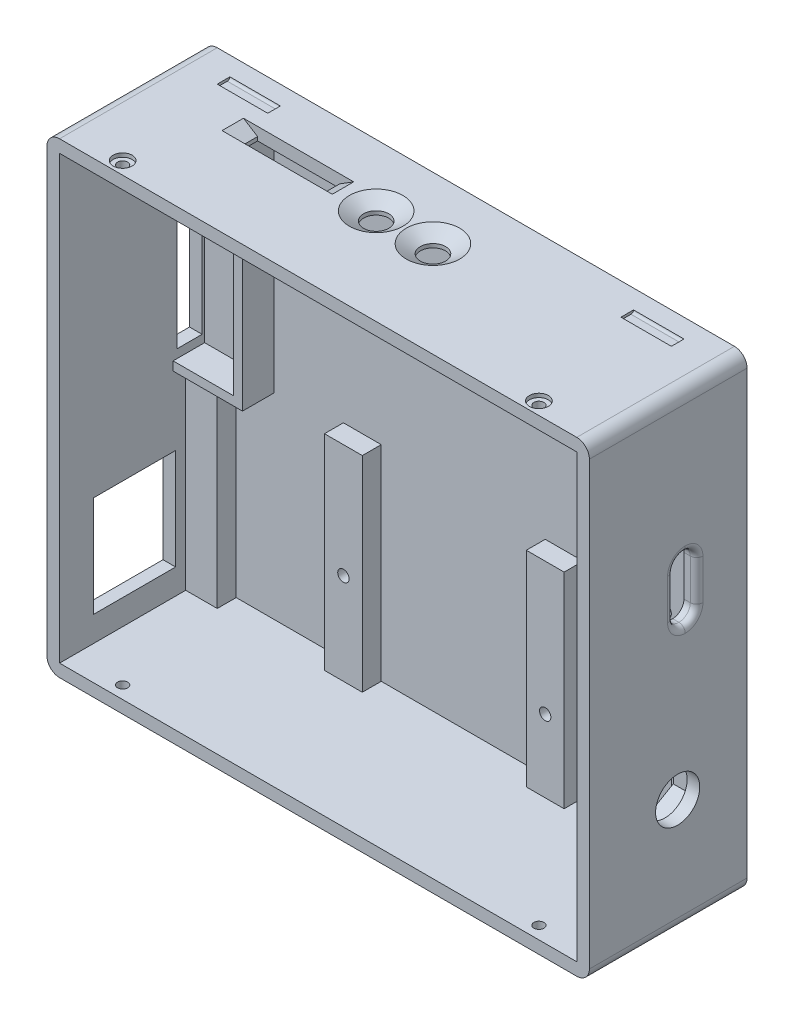
SolidWorks part; units mm, degrees
ref_plane "Front Plane" through (0, 0, 0) normal (0, 0, 1) x (1, 0, 0)
ref_plane "Top Plane" through (0, 0, 0) normal (0, 1, 0) x (1, 0, 0)
ref_plane "Right Plane" through (0, 0, 0) normal (1, 0, 0) x (0, 0, -1)
sketch "Sketch1" plane through (0, 0, 0) normal (0, 0, 1) x (1, 0, 0)
  line L1 (0, 0) -> (86, 0)
  line L2 (0, 0) -> (0, 74)
  line L3 (0, 74) -> (86, 74)
  line L4 (86, 0) -> (86, 74)
  dimension "D1" = 74
  dimension "D2" = 86
extrude "Boss-Extrude1" add sketch "Sketch1" along normal blind 25
sketch "Sketch3" plane through (0, 0, 25) normal (0, 0, 1) x (1, 0, 0)
  line L0 (0, 74) -> (0, 0) construction
  line L1 (2, 72) -> (84, 72)
  line L2 (2, 72) -> (2, 2)
  line L3 (2, 2) -> (84, 2)
  line L4 (84, 72) -> (84, 2)
  line L5 (86, 74) -> (0, 74) construction
  line L6 (0, 0) -> (86, 0) construction
  line L7 (86, 0) -> (86, 74) construction
  dimension "D1" = 2
  dimension "D2" = 2
  dimension "D3" = 2
  dimension "D4" = 2
extrude "Cut-Extrude1" cut sketch "Sketch3" against normal blind 23
sketch "Sketch4" plane through (0, 0, 2) normal (0, 0, 1) x (1, 0, 0)
  line L0 (84, 72) -> (2, 72) construction
  line L1 (84, 72) -> (76, 72)
  line L2 (84, 72) -> (84, 34.5)
  line L3 (84, 34.5) -> (76, 34.5)
  line L4 (76, 72) -> (76, 34.5)
  line L5 (13, 72) -> (11.6, 72)
  line L6 (13, 72) -> (13, 34.5)
  line L7 (13, 34.5) -> (11.6, 34.5)
  line L8 (11.6, 72) -> (11.6, 34.5)
  line L9 (84, 2) -> (84, 72) construction
  dimension "D1" = 37.5
  dimension "D2" = 8
  dimension "D3" = 71
  dimension "D4" = 1.4
extrude "Boss-Extrude2" add sketch "Sketch4" along normal blind 5
sketch "Sketch5" plane through (0, 0, 7) normal (0, 0, 1) x (1, 0, 0)
  line L0 (76, 72) -> (76, 34.5) construction
  line L1 (76, 54) -> (79, 54)
  line L2 (76, 54) -> (76, 62)
  line L3 (76, 62) -> (79, 62)
  line L4 (79, 54) -> (79, 62)
  line L5 (84, 72) -> (76, 72) construction
  line L6 (84, 34.5) -> (84, 72) construction
  line L7 (76, 34.5) -> (84, 34.5) construction
  line L8 (76, 41.5) -> (77, 41.5)
  line L9 (76, 41.5) -> (76, 45.5)
  line L10 (76, 45.5) -> (77, 45.5)
  line L11 (77, 41.5) -> (77, 45.5)
  dimension "D1" = 8
  dimension "D2" = 18
  dimension "D3" = 5
  dimension "D4" = 7
  dimension "D5" = 7
  dimension "D6" = 4
extrude "Cut-Extrude2" cut sketch "Sketch5" against normal blind 2
sketch "Sketch6" plane through (0, 0, 7) normal (0, 0, 1) x (1, 0, 0)
  line L0 (84, 72) -> (76, 72) construction
  line L2 (84, 34.5) -> (84, 72) construction
  circle A0 centre (80, 67.25) radius 1
  circle A1 centre (80, 39.25) radius 1
  dimension "D4" = 2
  dimension "D5" = 2
  dimension "D1" = 28
  dimension "D2" = 4.75
  dimension "D3" = 4
extrude "Cut-Extrude3" cut sketch "Sketch6" against normal blind 5
sketch "Sketch7" plane through (2, 0, 0) normal (1, 0, 0) x (0, 0, -1)
  line L1 (-2.4, 70.85) -> (-6.4, 70.85)
  line L2 (-2.4, 70.85) -> (-2.4, 35.85)
  line L3 (-2.4, 35.85) -> (-6.4, 35.85)
  line L4 (-6.4, 70.85) -> (-6.4, 35.85)
  line L5 (-2, 72) -> (-2, 2) construction
  line L6 (-2, 72) -> (-25, 72) construction
  dimension "D1" = 4
  dimension "D2" = 35
  dimension "D3" = 0.4
  dimension "D4" = 1.15
extrude "Cut-Extrude4" cut sketch "Sketch7" against normal blind 5
sketch "Sketch9" plane through (0, 0, 2) normal (0, 0, 1) x (1, 0, 0)
  line L0 (2, 2) -> (84, 2) construction
  line L1 (84, 34.5) -> (79, 34.5)
  line L2 (84, 34.5) -> (84, 2)
  line L3 (84, 2) -> (79, 2)
  line L4 (79, 34.5) -> (79, 2)
  line L6 (62, 2) -> (56, 2)
  line L7 (62, 2) -> (62, 34.5)
  line L8 (62, 34.5) -> (56, 34.5)
  line L9 (56, 2) -> (56, 34.5)
  line L10 (2, 2) -> (7, 2)
  line L11 (2, 2) -> (2, 34.5)
  line L12 (2, 34.5) -> (7, 34.5)
  line L13 (7, 2) -> (7, 34.5)
  line L14 (24, 2) -> (30, 2)
  line L15 (24, 2) -> (24, 34.5)
  line L16 (24, 34.5) -> (30, 34.5)
  line L17 (30, 2) -> (30, 34.5)
  dimension "D1" = 5
  dimension "D2" = 6
  dimension "D3" = 22
  dimension "D4" = 5
  dimension "D5" = 6
  dimension "D6" = 22
extrude "Boss-Extrude3" add sketch "Sketch9" along normal blind 3
sketch "Sketch10" plane through (0, 0, 5) normal (0, 0, 1) x (1, 0, 0)
  line L0 (84, 2) -> (84, 34.5) construction
  line L1 (56, 2) -> (62, 2) construction
  line L2 (27, 34.5) -> (27, 2) construction
  line L3 (30, 34.5) -> (24, 34.5) construction
  line L4 (24, 2) -> (30, 2) construction
  circle A0 centre (59, 13.5) radius 0.9
  circle A1 centre (27, 16.5) radius 0.9
  dimension "D3" = 1.8
  dimension "D4" = 1.8
  dimension "D1" = 25
  dimension "D2" = 11.5
  dimension "D5" = 14.5
extrude "Cut-Extrude6" cut sketch "Sketch10" against normal blind 4
fillet "Fillet1" radius 2 4 edges at (86, 74, 12.5) (0, 74, 12.5) (0, 0, 12.5) (86, 0, 12.5)
sketch "Sketch13" plane through (0, 72, 0) normal (0, -1, 0) x (-1, 0, 0)
  line L0 (-80.7121, -7.6) -> (-14.4298, -7.6) construction
  line L1 (-84, -7) -> (-76, -7) construction
  line L2 (-84, -7) -> (-84, -25) construction
  line L3 (-29, -7.6) -> (-16, -7.6)
  line L4 (-29, -7.6) -> (-29, -11)
  line L5 (-29, -11) -> (-16, -11)
  line L6 (-16, -7.6) -> (-16, -11)
  circle A0 centre (-37, -9.8) radius 2
  circle A1 centre (-46, -9.8) radius 2
  dimension "D5" = 4
  dimension "D6" = 4
  dimension "D1" = 0.6
  dimension "D2" = 13
  dimension "D3" = 68
  dimension "D4" = 3.4
  dimension "D7" = 9
  dimension "D8" = 47
  dimension "D9" = 2.8
  dimension "D10" = 2.8
extrude "Cut-Extrude9" cut sketch "Sketch13" against normal blind 4
chamfer "Chamfer1" distance 1.4 angle 58 4 edges at (29, 74, 9.3) (16, 74, 9.3) (37, 74, 7.8) (46, 74, 7.8) first distance on face at (29, 73, 9.3) first distance on face at (16, 73, 9.3) first distance on face at (37, 72, 7.8) first distance on face at (46, 72, 7.8)
sketch "Sketch14" plane through (0, 0, 0) normal (0, -1, 0) x (-1, 0, 0)
  line L0 (0, 0) -> (0, -25) construction
  line L1 (-86, -25) -> (-86, 0) construction
  line L2 (-2, -25) -> (-84, -25) construction
  circle A0 centre (-10, -23) radius 0.8
  circle A1 centre (-76, -23) radius 0.8
  dimension "D5" = 1.6
  dimension "D6" = 1.6
  dimension "D1" = 10
  dimension "D2" = 10
  dimension "D3" = 2
  dimension "D4" = 2
extrude "Cut-Extrude10" cut sketch "Sketch14" against normal blind 76
sketch "Sketch15" plane through (0, 0, 0) normal (0, -1, 0) x (-1, 0, 0)
  circle A0 centre (-10, -23) radius 1.5
  circle A1 centre (-76, -23) radius 1.5
  dimension "D1" = 3
  dimension "D2" = 3
extrude "Cut-Extrude11" cut sketch "Sketch15" against normal blind 0.6
sketch "Sketch16" plane through (0, 74, 0) normal (0, 1, 0) x (1, 0, 0)
  circle A0 centre (76, -23) radius 1.5
  circle A1 centre (10, -23) radius 1.5
  dimension "D1" = 3
  dimension "D2" = 3
extrude "Cut-Extrude12" cut sketch "Sketch16" against normal blind 0.6
sketch "Sketch20" plane through (0, 0, 2) normal (0, 0, 1) x (1, 0, 0)
  line L0 (2, 72) -> (2, 34.5) construction
  line L1 (13, 34.5) -> (2, 34.5)
  line L2 (13, 34.5) -> (13, 33.1)
  line L3 (13, 33.1) -> (2, 33.1)
  line L4 (2, 34.5) -> (2, 33.1)
  dimension "D1" = 1.4
extrude "Boss-Extrude6" add sketch "Sketch20" along normal blind 5
sketch "Sketch21" plane through (2, 0, 0) normal (1, 0, 0) x (0, 0, -1)
  line L0 (-5, 2) -> (-25, 2) construction
  line L1 (-6.6, 6) -> (-19.6, 6)
  line L2 (-6.6, 6) -> (-6.6, 22)
  line L3 (-6.6, 22) -> (-19.6, 22)
  line L4 (-19.6, 6) -> (-19.6, 22)
  line L5 (-5, 33.1) -> (-5, 2) construction
  dimension "D1" = 13
  dimension "D2" = 16
  dimension "D3" = 20
  dimension "D4" = 1.6
extrude "Cut-Extrude13" cut sketch "Sketch21" against normal blind 10
sketch "Sketch22" plane through (0, 0, 5) normal (0, 0, 1) x (1, 0, 0)
  line L0 (84, 18.25) -> (79, 18.25) construction
  line L1 (84, 2) -> (84, 34.5) construction
  line L2 (79, 34.5) -> (79, 2) construction
  line L4 (84, 24.25) -> (81, 24.25)
  line L5 (84, 24.25) -> (84, 12.25)
  line L6 (84, 12.25) -> (81, 12.25)
  line L7 (81, 24.25) -> (81, 12.25)
  dimension "D1" = 6
  dimension "D2" = 12
  dimension "D3" = 3
extrude "Boss-Extrude7" add sketch "Sketch22" along normal blind 12
sketch "Sketch23" plane through (81, 0, 0) normal (-1, 0, 0) x (0, 0, 1)
  line L0 (17, 24.25) -> (5, 12.25) construction
  line L2 (6.7, 15.7674) -> (11, 13.2848)
  line L3 (11, 13.2848) -> (15.3, 15.7674)
  line L4 (15.3, 15.7674) -> (15.3, 20.7326)
  line L5 (15.3, 20.7326) -> (11, 23.2152)
  line L6 (11, 23.2152) -> (6.7, 20.7326)
  line L7 (6.7, 20.7326) -> (6.7, 15.7674)
  circle A0 centre (11, 18.25) radius 4.3 construction
  dimension "D1" = 8.6
extrude "Cut-Extrude14" cut sketch "Sketch23" against normal blind 3
sketch "Sketch24" plane through (84, 0, 0) normal (-1, 0, 0) x (0, 0, 1)
  line L0 (15.3, 18.25) -> (6.7, 18.25) construction
  line L1 (15.3, 15.7674) -> (15.3, 20.7326) construction
  line L2 (6.7, 20.7326) -> (6.7, 15.7674) construction
  circle A0 centre (11, 18.25) radius 3.5
  dimension "D1" = 7
extrude "Cut-Extrude15" cut sketch "Sketch24" against normal blind 3
fillet "Fillet2" radius 3 4 edges at (82.5, 12.25, 5) (82.5, 24.25, 5) (82.5, 12.25, 17) (82.5, 24.25, 17)
sketch "Sketch27" plane through (84, 0, 0) normal (-1, 0, 0) x (0, 0, 1)
  line L0 (7, 34.5) -> (7, 72) construction
  line L1 (11.6, 51.5) -> (8, 51.5)
  line L2 (11.6, 51.5) -> (11.6, 41.5)
  line L3 (11.6, 41.5) -> (8, 41.5)
  line L4 (8, 51.5) -> (8, 41.5)
  line L5 (7, 72) -> (25, 72) construction
  dimension "D1" = 3.6
  dimension "D2" = 10
  dimension "D3" = 1
  dimension "D4" = 20.5
extrude "Cut-Extrude16" cut sketch "Sketch27" against normal blind 3
fillet "Fillet3" radius 1.8 4 edges at (85, 41.5, 8) (85, 41.5, 11.6) (85, 51.5, 8) (85, 51.5, 11.6)
fillet "Fillet4" radius 1 6 edges at (86, 50.9728, 8.5272) (86, 50.9728, 11.0728) (86, 46.5, 11.6) (86, 42.0272, 11.0728) (86, 42.0272, 8.5272) (86, 46.5, 8)
fillet "Fillet5" radius 2 9 edges at (84, 5.625, 5) (84, 11.3713, 5.8787) (84, 12.25, 11) (84, 13.1287, 16.1213) (84, 30.875, 5) (84, 25.1287, 5.8787) (84, 24.25, 11) (84, 23.3713, 16.1213) (84, 18.25, 17)
sketch "Sketch28" plane through (0, 0, 0) normal (0, -1, 0) x (-1, 0, 0)
  line L0 (-2, -25) -> (-2, 0) construction
  line L1 (-7, -5) -> (-15, -5)
  line L2 (-7, -5) -> (-7, -3)
  line L3 (-7, -3) -> (-15, -3)
  line L4 (-15, -5) -> (-15, -3)
  line L5 (-79, -5) -> (-71, -5)
  line L6 (-79, -5) -> (-79, -3)
  line L7 (-79, -3) -> (-71, -3)
  line L8 (-71, -5) -> (-71, -3)
  line L9 (-2, 0) -> (-84, 0) construction
  line L10 (-84, 0) -> (-84, -25) construction
  dimension "D1" = 5
  dimension "D2" = 8
  dimension "D3" = 2
  dimension "D4" = 3
  dimension "D5" = 2
  dimension "D6" = 8
  dimension "D7" = 5
  dimension "D8" = 3
extrude "Cut-Extrude17" cut sketch "Sketch28" against normal blind 0.4
sketch "Sketch29" plane through (0, 74, 0) normal (0, 1, 0) x (1, 0, 0)
  line L0 (84, -3) -> (2, -3) construction
  line L1 (84, -25) -> (84, 0) construction
  line L2 (2, 0) -> (2, -25) construction
  line L3 (84, 0) -> (2, 0) construction
  line L5 (79, -3) -> (71, -3)
  line L6 (79, -3) -> (79, -5)
  line L7 (79, -5) -> (71, -5)
  line L8 (71, -3) -> (71, -5)
  line L9 (7, -3) -> (15, -3)
  line L10 (7, -3) -> (7, -5)
  line L11 (7, -5) -> (15, -5)
  line L12 (15, -3) -> (15, -5)
  dimension "D1" = 3
  dimension "D2" = 8
  dimension "D3" = 5
  dimension "D4" = 2
  dimension "D5" = 8
  dimension "D6" = 5
extrude "Cut-Extrude18" cut sketch "Sketch29" against normal blind 0.4
fillet "Fillet6" radius 0.4 8 edges at (75, 0.4, 5) (75, 0.4, 3) (11, 0.4, 3) (11, 0.4, 5) (11, 73.6, 5) (11, 73.6, 3) (75, 73.6, 3) (75, 73.6, 5)
